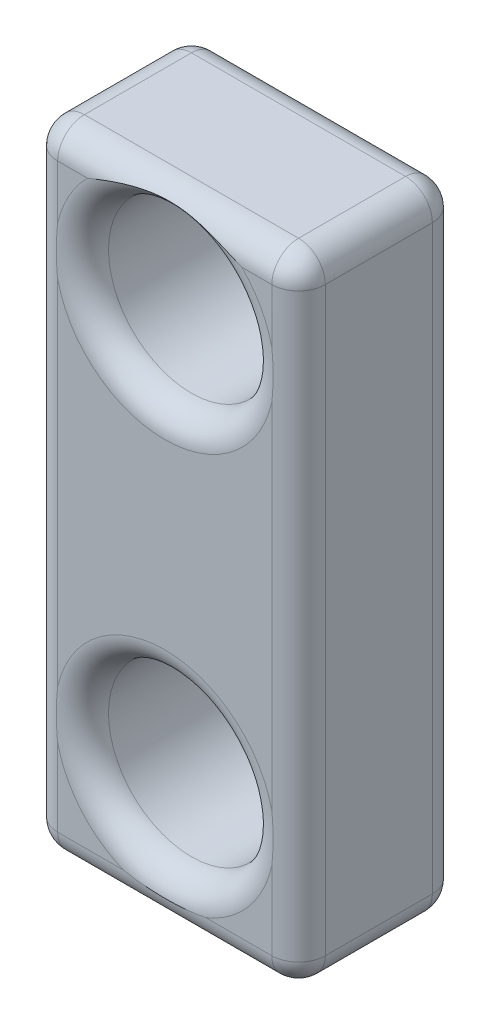
SolidWorks part; units mm, degrees
ref_plane "Front Plane" through (0, 0, 0) normal (0, 0, 1) x (1, 0, 0)
ref_plane "Top Plane" through (0, 0, 0) normal (0, 1, 0) x (1, 0, 0)
ref_plane "Right Plane" through (0, 0, 0) normal (1, 0, 0) x (0, 0, -1)
sketch "Sketch1" plane through (0, 0, 0) normal (0, 0, 1) x (1, 0, 0)
  line L0 (0, 4.3582) -> (0, -7.5) construction
  line L1 (2.5, 4.3582) -> (-2.5, 4.3582)
  line L2 (2.5, 4.3582) -> (2.5, -7.5)
  line L3 (2.5, -7.5) -> (-2.5, -7.5)
  line L4 (-2.5, 4.3582) -> (-2.5, -7.5)
  circle A0 centre (0, 2.4009) radius 1.55
  circle A2 centre (0, -5.0991) radius 1.55
  point P0 (0, 0)
  dimension "D3" = 3.1
  dimension "D1" = 5
extrude "Boss-Extrude1" add sketch "Sketch1" along normal blind 3
fillet "Fillet1" radius 0.5 16 edges at (2.5, -7.5, 1.5) (2.5, 4.3582, 1.5) (-2.5, 4.3582, 1.5) (-2.5, -7.5, 1.5) (1.55, -5.0991, 0) (0, -7.5, 0) (2.5, -1.5709, 0) (0, 4.3582, 0) (-2.5, -1.5709, 0) (1.55, 2.4009, 0) (1.55, -5.0991, 3) (1.55, 2.4009, 3) (0, -7.5, 3) (0, 4.3582, 3) (2.5, -1.5709, 3) (-2.5, -1.5709, 3)
